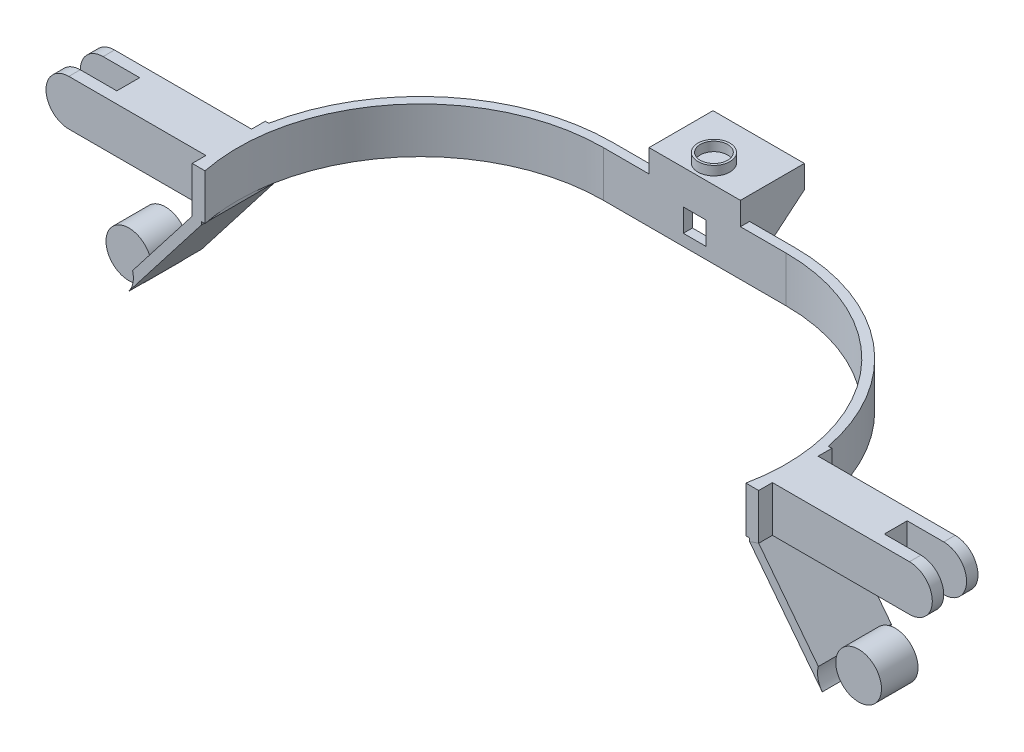
SolidWorks part; units mm, degrees
ref_plane "Front" through (0, 0, 0) normal (0, 0, 1) x (1, 0, 0)
ref_plane "Top" through (0, 0, 0) normal (0, 1, 0) x (1, 0, 0)
ref_plane "Right" through (0, 0, 0) normal (1, 0, 0) x (0, 0, -1)
sketch "草图2" plane through (0, 0, 0) normal (0, 1, 0) x (1, 0, 0)
  line L0 (-40, 0) -> (40, 0) construction
  line L1 (-40, 80) -> (40, 80)
  line L2 (-40, -80) -> (40, -80)
  line L3 (-40, 0) -> (40, 0) construction
  line L4 (-40, 84) -> (40, 84)
  line L5 (-40, -84) -> (40, -84)
  arc A0 (-40, 80) -> (-40, -80) centre (-40, 0) ccw
  arc A1 (40, -80) -> (40, 80) centre (40, 0) ccw
  arc A2 (-40, 84) -> (-40, -84) centre (-40, 0) ccw
  arc A3 (40, -84) -> (40, 84) centre (40, 0) ccw
  point P2 (0, 0)
  point P10 (0, 0)
extrude "凸台-拉伸1" add sketch "草图2" along normal blind 20
sketch "草图8" plane through (0, 20, 0) normal (0, 1, 0) x (1, 0, 0)
  line L0 (0, 0) -> (-175.2062, 0) construction
  line L1 (-124, 16) -> (-120, 16)
  line L2 (-124, 16) -> (-124, -16)
  line L3 (-124, -16) -> (-120, -16)
  line L4 (-120, 16) -> (-120, -16)
  dimension "D1" = 4
  dimension "D2" = 32
  dimension "D3" = 16
sketch "草图9" plane through (0, 0, 0) normal (0, 0, 1) x (1, 0, 0)
  line L0 (0, 0) -> (-176.3582, 0) construction
  line L1 (-155, -40) -> (155, -40) construction
  line L2 (0, 0) -> (0, -149.7853) construction
  line L3 (-124, 20) -> (-124, 0)
  line L4 (-124, 0) -> (-155, -40)
  point P11 (155, -40)
  dimension "D1" = 40
  dimension "D2" = 310
  dimension "D3" = 155
sketch "草图11" plane through (0, 20, 0) normal (0, 1, 0) x (1, 0, 0)
  line L0 (0, 0) -> (130.9327, 0) construction
  line L1 (0, 0) -> (0, 51.5924) construction
  line L3 (124, 16) -> (120, 16)
  line L4 (124, 16) -> (124, -16)
  line L5 (124, -16) -> (120, -16)
  line L6 (120, 16) -> (120, -16)
  dimension "D1" = 124
  dimension "D2" = 4
  dimension "D3" = 32
  dimension "D4" = 16
sketch "草图18" plane through (0, 0, -84) normal (0, 0, -1) x (-1, 0, 0)
  line L6 (-5, 5) -> (5, 5) construction
  line L7 (-5, 15) -> (5, 15)
  line L8 (-5, 15) -> (-5, 5)
  line L9 (-5, 5) -> (5, 5)
  line L10 (5, 15) -> (5, 5)
  dimension "D1" = 10
  dimension "D2" = 5
  dimension "D3" = 5
  dimension "D4" = 10
extrude "切除-拉伸6" cut sketch "草图18" against normal blind 10
sketch "草图20" plane through (0, 20, 0) normal (0, 1, 0) x (1, 0, 0)
  line L0 (0, 80) -> (0, 120.4936) construction
  line L1 (40, 80) -> (-40, 80) construction
  line L2 (40, 84) -> (-40, 84) construction
  line L3 (-20, 84) -> (20, 84)
  line L4 (-20, 84) -> (-20, 80)
  line L5 (-20, 80) -> (20, 80)
  line L6 (20, 84) -> (20, 80)
  dimension "D1" = 40
  dimension "D2" = 20
extrude "凸台-拉伸5" add sketch "草图20" along normal blind 10
sweep "扫描1" add profiles "草图8" path "草图9"
sketch "草图25" plane through (0, 20, 0) normal (0, 1, 0) x (1, 0, 0)
  line L1 (-122.4621, -16) -> (124.4416, -16)
  line L2 (-122.4621, -16) -> (-122.4621, -91.0614)
  line L3 (-122.4621, -91.0614) -> (124.4416, -91.0614)
  line L4 (124.4416, -16) -> (124.4416, -91.0614)
extrude "切除-拉伸7" cut sketch "草图25" against normal blind 30
sketch "草图26" plane through (-124, 0, 0) normal (-1, 0, 0) x (0, 0, 1)
  line L0 (0, 0) -> (0, 49.4965) construction
  line L1 (16, 0) -> (-16, 0) construction
  line L2 (-16, 20) -> (16, 20) construction
  line L3 (-10, 20) -> (10, 20)
  line L4 (-10, 20) -> (-10, 0)
  line L5 (-10, 0) -> (10, 0)
  line L6 (10, 20) -> (10, 0)
  dimension "D1" = 20
  dimension "D2" = 10
sketch "草图27" plane through (0, 0, 0) normal (0, 0, 1) x (1, 0, 0)
  line L0 (124, 20) -> (124, 0)
  line L1 (0, 0) -> (0, -70.6099) construction
  line L2 (124, 0) -> (155, -40)
  point P4 (-155, -40)
  point P9 (155, -40)
sweep "扫描2" add profiles "草图11" path "草图27"
extrude "凸台-拉伸6" add sketch "草图26" along normal blind 70
sketch "草图28" plane through (124, 0, 0) normal (1, 0, 0) x (0, 0, -1)
  line L0 (0, 0) -> (0, 32.1211) construction
  line L1 (-16, 20) -> (16, 20) construction
  line L2 (-10, 20) -> (10, 20)
  line L3 (-10, 20) -> (-10, 0)
  line L4 (-10, 0) -> (10, 0)
  line L5 (10, 20) -> (10, 0)
  line L6 (16, 0) -> (-16, 0) construction
  dimension "D1" = 20
  dimension "D2" = 10
extrude "凸台-拉伸7" add sketch "草图28" along normal blind 70
sketch "草图29" plane through (0, 20, 0) normal (0, 1, 0) x (1, 0, 0)
  line L0 (-194, 0) -> (194, 0) construction
  line L1 (-194, -10) -> (-194, 10) construction
  line L2 (194, 10) -> (194, -10) construction
  line L4 (-194, 5) -> (-168, 5)
  line L5 (-194, 5) -> (-194, -5)
  line L6 (-194, -5) -> (-168, -5)
  line L7 (-168, 5) -> (-168, -5)
  line L8 (194, 5) -> (168, 5)
  line L9 (194, 5) -> (194, -5)
  line L10 (194, -5) -> (168, -5)
  line L11 (168, 5) -> (168, -5)
  dimension "D1" = 10
  dimension "D2" = 26
  dimension "D3" = 5
  dimension "D4" = 5
  dimension "D5" = 10
  dimension "D6" = 26
extrude "切除-拉伸8" cut sketch "草图29" against normal blind 20
sketch "草图31" plane through (0, 0, 16) normal (0, 0, 1) x (1, 0, 0)
  line L0 (-133.6037, -18.9217) -> (-151.8383, -42.4503) construction
  line L1 (-120, -1.3686) -> (-151.8383, -42.4503) construction
  line L2 (-151.8383, -42.4503) -> (-187.4708, -14.8352) construction
  line L3 (139.7463, -26.8477) -> (151.8383, -42.4503) construction
  line L4 (120, -1.3686) -> (151.8383, -42.4503) construction
  line L5 (151.8383, -42.4503) -> (173.4376, -25.7109) construction
  circle A0 centre (-159.7425, -36.3246) radius 10
  circle A1 centre (159.7425, -36.3246) radius 10
extrude "切除-拉伸10" cut sketch "草图31" against normal through all
sketch "草图32" plane through (0, 0, 0) normal (0, 0, 1) x (1, 0, 0)
  circle A0 centre (-159.7425, -36.3246) radius 10
  circle A1 centre (159.7425, -36.3246) radius 10
extrude "凸台-拉伸8" add sketch "草图32" along normal mid plane 16
sketch "草图33" plane through (0, 0, 10) normal (0, 0, 1) x (1, 0, 0)
  line L1 (-184, 20) -> (-199.3887, 20)
  line L3 (-184, 0) -> (-199.3887, 0)
  line L4 (-199.3887, 20) -> (-199.3887, 0)
  line L5 (184, 20) -> (198.4135, 20)
  line L7 (184, 0) -> (198.4135, 0)
  line L8 (198.4135, 20) -> (198.4135, 0)
  arc A0 (-184, 20) -> (-184, 0) centre (-184, 10) ccw
  arc A1 (184, 0) -> (184, 20) centre (184, 10) ccw
extrude "切除-拉伸11" cut sketch "草图33" against normal through all
sketch "草图34" plane through (0, 0, -84) normal (0, 0, -1) x (-1, 0, 0)
  line L0 (-40, 0) -> (40, 0) construction
  line L1 (20, 30) -> (-20, 30)
  line L2 (20, 30) -> (20, 20)
  line L3 (12, 20) -> (-12, 20)
  line L4 (-20, 30) -> (-20, 20)
  line L6 (20, 20) -> (20, 0)
  line L7 (20, 0) -> (12, 0)
  line L8 (12, 20) -> (12, 0)
  line L11 (-20, 20) -> (-20, 0)
  line L12 (-20, 0) -> (-12, 0)
  line L13 (-12, 20) -> (-12, 0)
  dimension "D1" = 8
  dimension "D2" = 8
extrude "凸台-拉伸9" add sketch "草图34" along normal blind 24
sketch "草图35" plane through (20, 0, 0) normal (1, 0, 0) x (0, 0, -1)
  line L0 (108, 20) -> (84, 0)
  line L1 (108, 30) -> (108, 0) construction
  line L2 (84, 0) -> (110.8052, 0)
  line L3 (110.8052, 0) -> (108, 20)
  dimension "D1" = 10
extrude "切除-拉伸12" cut sketch "草图35" against normal through all
sketch "草图36" plane through (0, 30, 0) normal (0, 1, 0) x (1, 0, 0)
  line L0 (-20, 80) -> (20, 80) construction
  circle A0 centre (0, 88.4) radius 6
  circle A1 centre (0, 88.4) radius 7
  dimension "D1" = 8.4
extrude "凸台-拉伸10" add sketch "草图36" along normal blind 4
